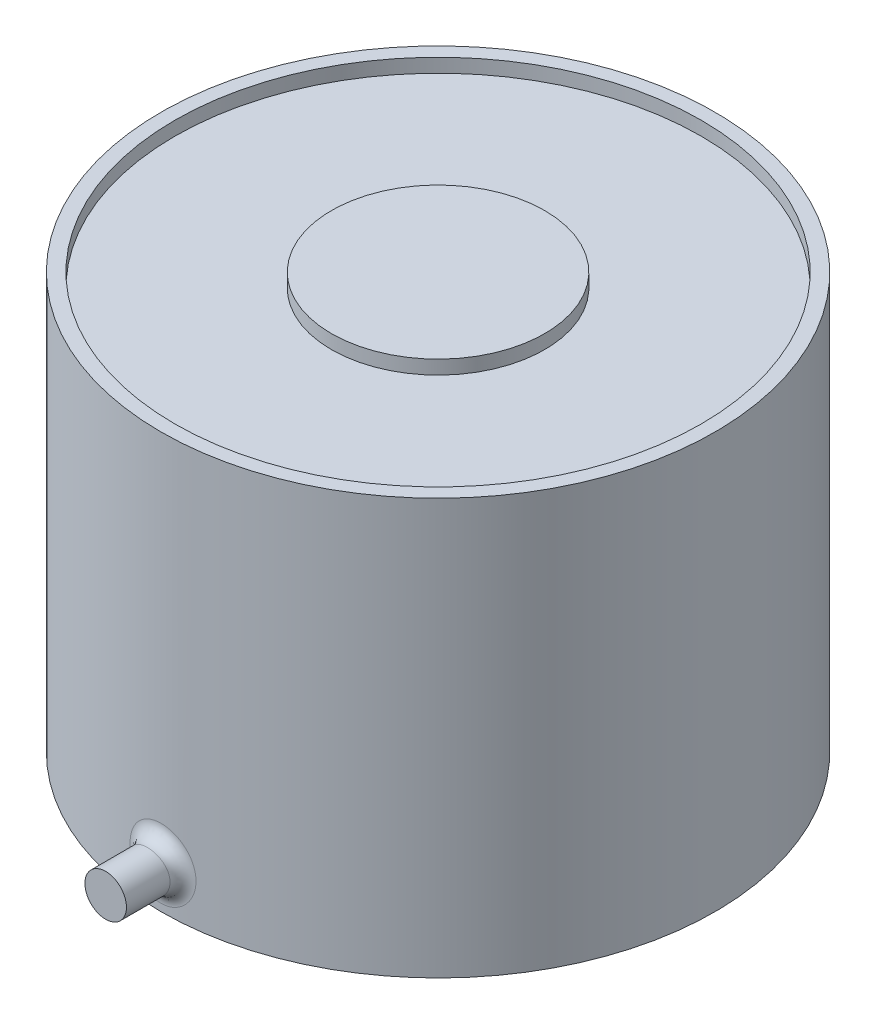
SolidWorks part; units mm, degrees
ref_plane "Plan de face" through (0, 0, 0) normal (0, 0, 1) x (1, 0, 0)
ref_plane "Plan de dessus" through (0, 0, 0) normal (0, 1, 0) x (1, 0, 0)
ref_plane "Plan de droite" through (0, 0, 0) normal (1, 0, 0) x (0, 0, -1)
sketch "Esquisse1" plane through (0, 0, 0) normal (0, 1, 0) x (1, 0, 0)
  circle A0 centre (0, 0) radius 10
  dimension "D1" = 20
extrude "Boss.-Extru.1" add sketch "Esquisse1" along normal blind 15
sketch "Esquisse2" plane through (0, 15, 0) normal (0, 1, 0) x (1, 0, 0)
  circle A0 centre (0, 0) radius 9.5
  circle A1 centre (0, 0) radius 3.85
  dimension "D1" = 7.7
  dimension "D2" = 19
extrude "Enlèv. mat.-Extru.1" cut sketch "Esquisse2" against normal blind 0.5
ref_plane "Plan1" through (0, 0, 9) normal (0, 0, 1) x (1, 0, 0)
sketch "Esquisse3" plane through (0, 0, 9) normal (0, 0, 1) x (1, 0, 0)
  circle A0 centre (0, 1.5138) radius 0.75
  dimension "D1" = 1.5
extrude "Boss.-Extru.2" add sketch "Esquisse3" along normal blind 3
fillet "Congé1" radius 0.5 1 edges at (0.7304, 1.684, 9.9733)
